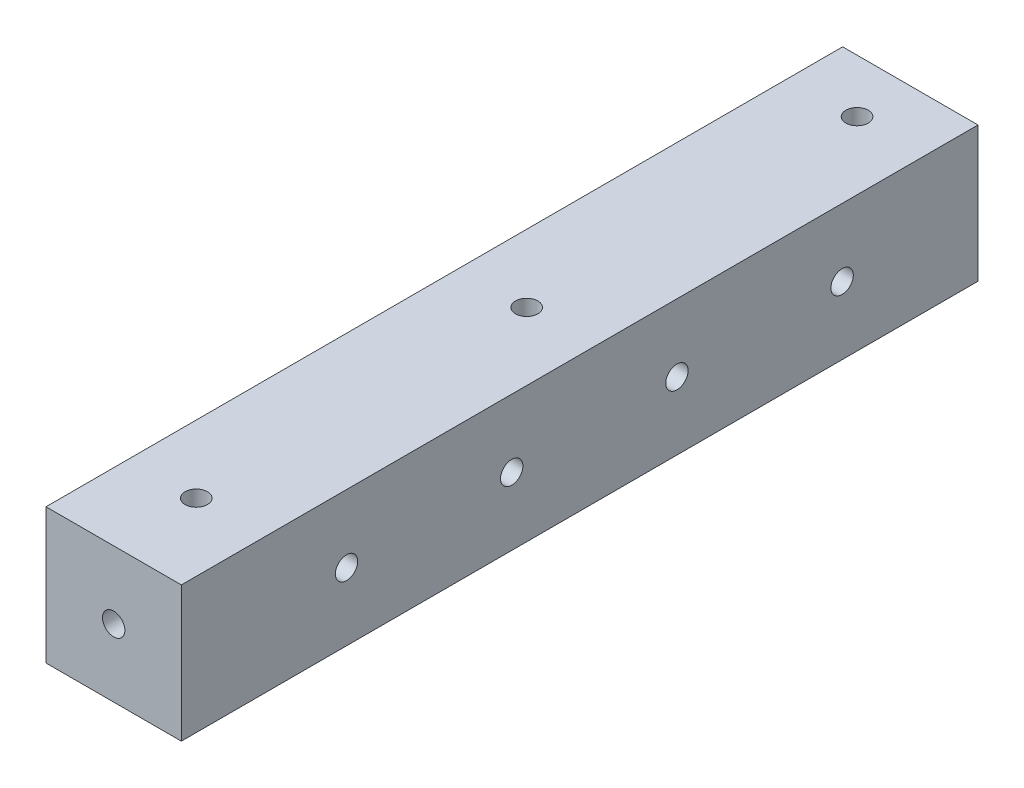
SolidWorks part; units mm, degrees
material "6061 Alloy"
ref_plane "Front Plane" through (0, 0, 0) normal (0, 0, 1) x (1, 0, 0)
ref_plane "Top Plane" through (0, 0, 0) normal (0, 1, 0) x (1, 0, 0)
ref_plane "Right Plane" through (0, 0, 0) normal (1, 0, 0) x (0, 0, -1)
sketch "Sketch1" plane through (0, 0, 0) normal (0, 0, 1) x (1, 0, 0)
  line L1 (-12.7, -12.7) -> (12.7, -12.7)
  line L2 (-12.7, -12.7) -> (-12.7, 12.7)
  line L3 (-12.7, 12.7) -> (12.7, 12.7)
  line L4 (12.7, -12.7) -> (12.7, 12.7)
  line L5 (-12.7, -12.7) -> (12.7, 12.7) construction
  line L6 (-12.7, 12.7) -> (12.7, -12.7) construction
  point P0 (0, 0)
  dimension "D1" = 25.4
extrude "Boss-Extrude1" add sketch "Sketch1" along normal mid plane 155
sketch "Sketch2" plane through (0, 0, 77.5) normal (0, 0, 1) x (1, 0, 0)
  point P0 (0, 0)
sketch "Sketch4" plane through (12.7, 0, 0) normal (1, 0, 0) x (0, 0, -1)
  line L0 (-77.5, -12.7) -> (-77.5, 12.7) construction
  point P0 (-46.5, 0)
  point P1 (-15.5, 0)
  point P2 (15.5, 0)
  point P3 (46.5, 0)
  dimension "D1" = 31
  dimension "D2" = 31
  dimension "D3" = 31
  dimension "D4" = 31
sketch "Sketch5" plane through (0, -12.7, 0) normal (0, -1, 0) x (1, 0, 0)
  line L0 (-12.7, 77.5) -> (12.7, 77.5) construction
  line L1 (-12.7, -77.5) -> (12.7, -77.5) construction
  point P0 (0, 62)
  point P1 (0, 0)
  point P2 (0, -62)
  dimension "D1" = 15.5
  dimension "D2" = 15.5
hole_wizard "M5x0.8 Tapped Hole3" positions "Sketch6" profile "Sketch8" tap size "M5x0.8" standard "ANSI Metric" end condition through all
sketch "Sketch6" plane through (12.7, 0, 0) normal (1, 0, 0) x (0, 0, -1)
  point P0 (-46.5, 0)
  point P3 (-15.5, 0)
  point P6 (15.5, 0)
  point P9 (46.5, 0)
sketch "Sketch8" plane through (12.7, 0, 46.5) normal (0, 1, 0) x (0, 0, -1)
  line L0 (0, 0) -> (0, 25.4)
  line L1 (0, 25.4) -> (2.1, 25.4)
  line L2 (2.1, 25.4) -> (2.1, 0)
  line L5 (2.1, 0) -> (0, 0)
  line L11 (0, -6.35) -> (0, 107.95) construction
  dimension "Thru Tap Drill Dia." = 4.2
  dimension "Thru Tap Drill Depth" = 25.4
hole_wizard "M5x0.8 Tapped Hole2" positions "Sketch9" profile "Sketch10" tap size "M5x0.8" standard "ANSI Metric" end condition through all
sketch "Sketch9" plane through (0, -12.7, 0) normal (0, -1, 0) x (-1, 0, 0)
  point P0 (0, -62)
  point P3 (0, 0)
  point P6 (0, 62)
sketch "Sketch10" plane through (0, -12.7, 62) normal (1, 0, 0) x (0, 0, -1)
  line L0 (0, 0) -> (0, 25.4)
  line L1 (0, 25.4) -> (2.1, 25.4)
  line L2 (2.1, 25.4) -> (2.1, 0)
  line L5 (2.1, 0) -> (0, 0)
  line L11 (0, -6.35) -> (0, 107.95) construction
  dimension "Thru Tap Drill Dia." = 4.2
  dimension "Thru Tap Drill Depth" = 25.4
hole_wizard "M5x0.8 Tapped Hole1" positions "Sketch11" profile "Sketch12" tap size "M5x0.8" standard "ANSI Metric"
sketch "Sketch11" plane through (0, 0, 77.5) normal (0, 0, 1) x (1, 0, 0)
  point P0 (0, 0)
sketch "Sketch12" plane through (0, 0, 77.5) normal (1, 0, 0) x (0, -1, 0)
  line L0 (0, 0) -> (0, 11.2618)
  line L1 (0, 11.2618) -> (2.1, 10)
  line L2 (2.1, 10) -> (2.1, 0)
  line L5 (2.1, 0) -> (0, 0)
  line L10 (0, 11.2618) -> (-2.1, 10) construction
  line L11 (0, -6.35) -> (0, 107.95) construction
  dimension "Tap Drill Dia." = 4.2
  dimension "Tap Drill Depth" = 10
  dimension "Drill Angle" = 118
sketch "Sketch13" plane through (0, 12.7, 0) normal (0, 1, 0) x (1, 0, 0)
  line L0 (12.7, -77.5) -> (12.7, 77.5) construction
  line L1 (12.7, 72) -> (-12.7, 72)
  line L2 (12.7, 72) -> (12.7, 77.5)
  line L3 (12.7, 77.5) -> (-12.7, 77.5)
  line L4 (-12.7, 72) -> (-12.7, 77.5)
  line L5 (-12.7, -77.5) -> (-12.7, 77.5) construction
  line L6 (12.7, 77.5) -> (-12.7, 77.5) construction
  circle A0 centre (0, 62) radius 2.1 construction
  dimension "D1" = 10
extrude "Cut-Extrude1" cut sketch "Sketch13" against normal through all
